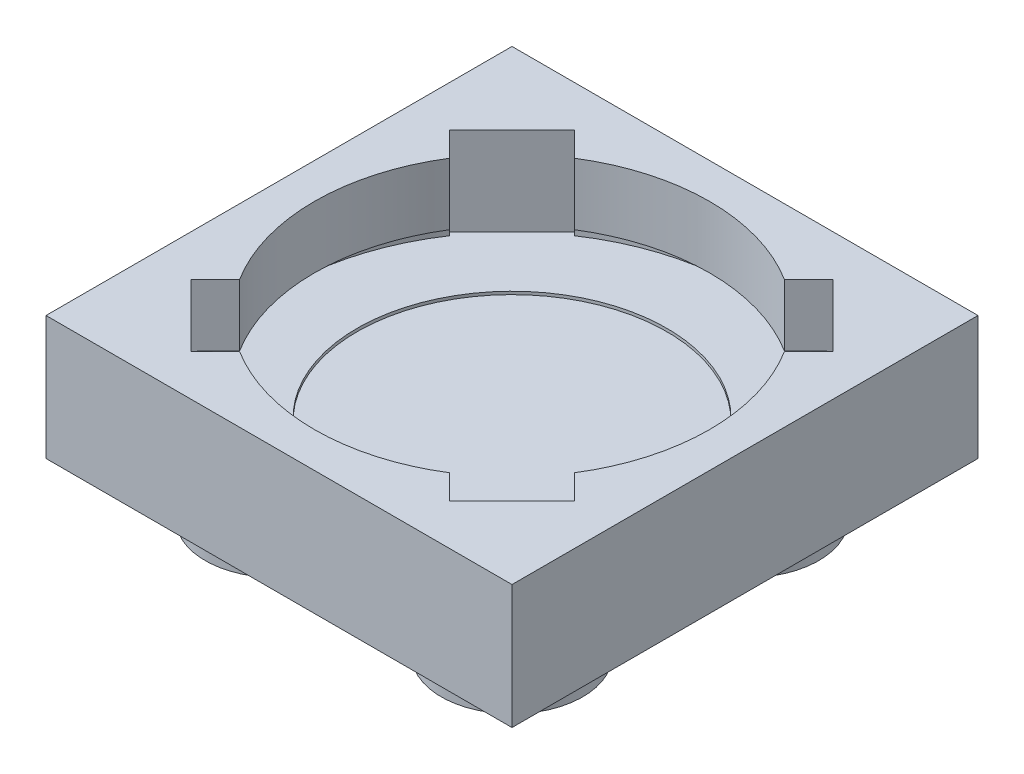
SolidWorks part; units mm, degrees
ref_plane "Front Plane" through (0, 0, 0) normal (0, 0, 1) x (1, 0, 0)
ref_plane "Top Plane" through (0, 0, 0) normal (0, 1, 0) x (1, 0, 0)
ref_plane "Right Plane" through (0, 0, 0) normal (1, 0, 0) x (0, 0, -1)
sketch "Sketch2" plane through (0, 0, 0) normal (0, 1, 0) x (1, 0, 0)
  line L1 (0, 0) -> (15.8, 0)
  line L2 (0, 0) -> (0, 15.8)
  line L3 (0, 15.8) -> (15.8, 15.8)
  line L4 (15.8, 0) -> (15.8, 15.8)
  dimension "D1" = 15.8
  dimension "D2" = 15.8
extrude "Boss-Extrude2" add sketch "Sketch2" against normal blind 4.2
sketch "Sketch4" plane through (0, 0, 0) normal (0, 1, 0) x (1, 0, 0)
  line L0 (15.8, 0) -> (15.8, 15.8) construction
  line L1 (14.6, 14.6) -> (1.2, 14.6)
  line L2 (14.6, 14.6) -> (14.6, 1.2)
  line L3 (14.6, 1.2) -> (1.2, 1.2)
  line L4 (1.2, 14.6) -> (1.2, 1.2)
  line L5 (0, -55) -> (0, 55) construction
  line L6 (-55, 0) -> (55, 0) construction
  line L7 (15.8, 15.8) -> (0, 15.8) construction
  dimension "D1" = 1.2
  dimension "D2" = 1.2
  dimension "D3" = 1.2
  dimension "D4" = 1.2
extrude "Cut-Extrude1" cut sketch "Sketch4" against normal offset from surface (3 mm away) 1.2 up to face at (7.9, -4.2, -7.9)
sketch "Sketch6" plane through (0, -4.2, 0) normal (0, -1, 0) x (-1, 0, 0)
  line L0 (-15.8, 0) -> (-15.8, 15.8) construction
  line L1 (-15.8, 15.8) -> (0, 15.8) construction
  circle A0 centre (-11.9, 11.9) radius 2.4
  dimension "D1" = 4.8
  dimension "D2" = 3.9
  dimension "D3" = 3.9
extrude "Boss-Extrude4" add sketch "Sketch6" along normal blind 1.8
pattern_linear "LPattern1" count 2 spacing 8 along (0, 0, 1) count 2 spacing 8 along (-1, 0, 0) of "Boss-Extrude4"
sketch "Sketch8" plane through (0, -3, 0) normal (0, 1, 0) x (1, 0, 0)
  line L0 (0, -3.3) -> (0, 3.3) construction
  line L1 (-3.3, 0) -> (3.3, 0) construction
  circle A0 centre (7.9, 7.9) radius 5.25
  point P27 (7.9, 7.9)
  dimension "D1" = 10.5
  dimension "D2" = 7.9
  dimension "D3" = 7.9
extrude "Cut-Extrude2" cut sketch "Sketch8" against normal blind 0.1
sketch "Sketch11" plane through (0, -3, 0) normal (0, 1, 0) x (1, 0, 0)
  line L1 (1.2, 14.6) -> (14.6, 14.6)
  line L2 (1.2, 14.6) -> (1.2, 1.2)
  line L3 (1.2, 1.2) -> (14.6, 1.2)
  line L4 (14.6, 14.6) -> (14.6, 1.2)
  circle A0 centre (7.9, 7.9) radius 6.7
  line M3 (14.6, 1.2) -> (14.6, 14.6)
  line M4 (14.6, 14.6) -> (1.2, 14.6)
  line M5 (1.2, 14.6) -> (1.2, 1.2)
  line M6 (1.2, 1.2) -> (14.6, 1.2)
extrude "Boss-Extrude9" add sketch "Sketch11" along normal up to surface (3 mm away) contours A0 L1 M5 | A0 L4 M4 | A0 L2 M6 | A0 L3 M3 region at (2.6966, -3, -13.1034) region at (13.1034, -3, -13.1034) region at (2.6966, -3, -2.6966) region at (13.1034, -3, -2.6966) up to face at (7.9, 0, -7.9)
sketch "Sketch12" plane through (0, 0, 0) normal (0, 1, 0) x (1, 0, 0)
  line L0 (0, 15.8) -> (3.1624, 12.6376)
  line L1 (0, -3.3) -> (0, 3.3) construction
  line L2 (15.8, 15.8) -> (0, 15.8) construction
  line L3 (2.1017, 11.577) -> (4.223, 13.6983)
  line L4 (2.1017, 11.577) -> (4.223, 13.6983)
  line L5 (2.1017, 11.577) -> (1.3946, 12.2841)
  line L6 (4.223, 13.6983) -> (3.5159, 14.4054)
  line L7 (1.3946, 12.2841) -> (3.5159, 14.4054)
  line L8 (2.1017, 11.577) -> (4.223, 13.6983)
  line L9 (2.1017, 11.577) -> (2.4236, 11.2551)
  line L10 (4.223, 13.6983) -> (4.5449, 13.3764)
  line L11 (2.4236, 11.2551) -> (4.5449, 13.3764)
  circle A0 centre (7.9, 7.9) radius 6.7 construction
  point P11 (3.1624, 12.6376)
  circle M2 centre (7.9, 7.9) radius 6.7
  dimension "D1" = 1
  dimension "D2" = 1.5
extrude "Cut-Extrude3" cut sketch "Sketch12" against normal offset from surface (3 mm away) 1.2 contours L7 L5 L3 L0 | L3 L9 M2 | L10 L3 M2 | L7 L0 L3 L6 | L9 L11 L10 M2 region at (3.3392, 0, -13.5215) region at (2.2785, 0, -12.4608) region at (2.4022, 0, -11.8054) region at (3.9946, 0, -13.3978) region at (3.341, 0, -12.459) up to face at (11.9, -4.2, -6.3)
ref_axis "Axis2" through (7.9, 0, -7.9) along (0, -1, 0)
pattern_circular "CirPattern3" count 4 every 90 about axis through (7.9, 0, -7.9) along (0, -1, 0) of "Cut-Extrude3"
sketch "Sketch18" plane through (-5.4447, 0, -5.4447) normal (0.7071, 0, 0.7071) x (0.7071, 0, -0.7071)
  line L0 (11.1723, 0) -> (11.1723, -3)
  line L1 (9.6723, 0) -> (12.6723, 0) construction
  line L2 (9.6723, -3) -> (12.6723, -3) construction
ref_plane "Plane2" through (7.9, 0, -7.9) normal (-0.7071, 0, 0.7071) x (0.7071, 0, 0.7071)
sketch "Sketch19" plane through (7.9, 0, -7.9) normal (-0.7071, 0, 0.7071) x (0.7071, 0, 0.7071)
  line L1 (-7.7, -3) -> (-6.2155, -3)
  line L2 (-7.7, -3) -> (-7.7, -2.1)
  line L3 (-7.7, -2.1) -> (-6.2155, -2.1)
  line L4 (-6.2155, -3) -> (-6.2155, -2.1)
  dimension "D1" = 0.9
revolve "Cut-Revolve1" cut sketch "Sketch19" angle 360 about axis through (7.9, 0, -7.9) along (0, -1, 0)
